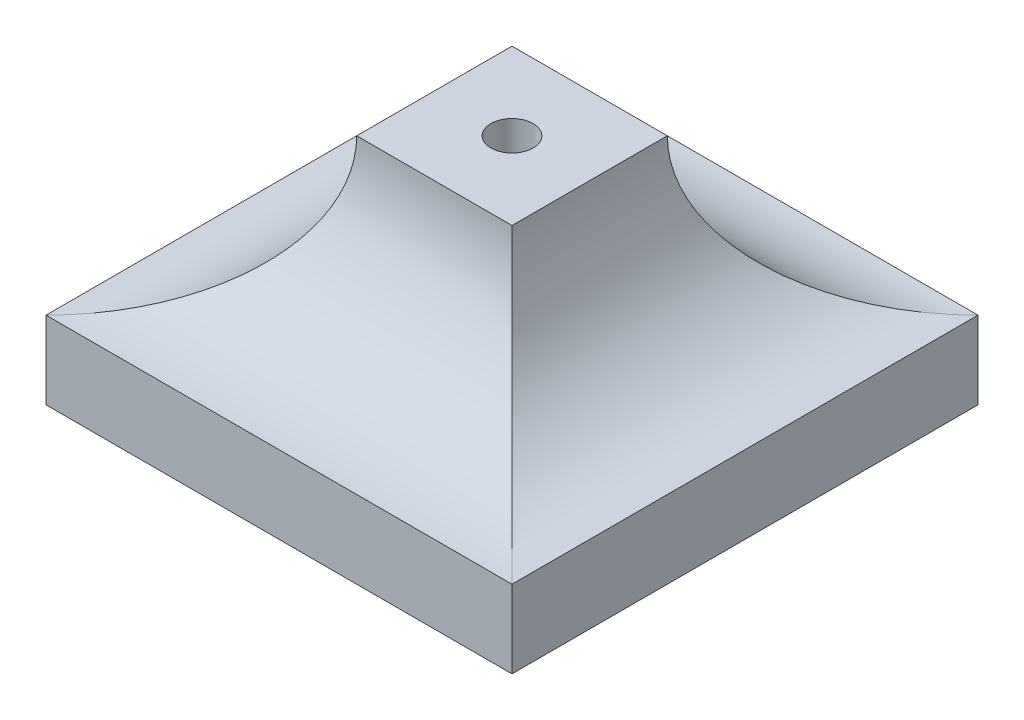
SolidWorks part; units mm, degrees
ref_plane "Front Plane" through (0, 0, 0) normal (0, 0, 1) x (1, 0, 0)
ref_plane "Top Plane" through (0, 0, 0) normal (0, 1, 0) x (1, 0, 0)
ref_plane "Right Plane" through (0, 0, 0) normal (1, 0, 0) x (0, 0, -1)
sketch "Sketch1" plane through (0, 0, 0) normal (0, 1, 0) x (1, 0, 0)
  line L1 (-19.05, 19.05) -> (19.05, 19.05)
  line L2 (-19.05, 19.05) -> (-19.05, -19.05)
  line L3 (-19.05, -19.05) -> (19.05, -19.05)
  line L4 (19.05, 19.05) -> (19.05, -19.05)
  line L5 (-19.05, 19.05) -> (19.05, -19.05) construction
  line L6 (-19.05, -19.05) -> (19.05, 19.05) construction
  point P0 (0, 0)
  dimension "D1" = 38.1
extrude "Boss-Extrude1" add sketch "Sketch1" along normal blind 6.35
sketch "Sketch2" plane through (0, 0, 19.05) normal (0, 0, 1) x (1, 0, 0)
  line L0 (-19.05, 6.35) -> (19.05, 6.35)
  line L1 (-6.35, 19.05) -> (6.35, 19.05)
  arc A0 (-19.05, 6.35) -> (-6.35, 19.05) centre (-19.05, 19.05) ccw
  arc A1 (19.05, 6.35) -> (6.35, 19.05) centre (19.05, 19.05) cw
  dimension "D1" = 12.7
extrude "Boss-Extrude2" add sketch "Sketch2" against normal up to surface (38.1 mm away) up to face at (0, 3.175, -19.05)
sketch "Sketch3" plane through (19.05, 0, 0) normal (1, 0, 0) x (0, 0, -1)
  line L0 (-19.05, 6.35) -> (-19.05, 19.05)
  line L1 (-19.05, 19.05) -> (-6.35, 19.05)
  line L2 (0, 0) -> (0, 19.05) construction
  line L3 (-19.05, 0) -> (19.05, 0) construction
  line L4 (19.05, 6.35) -> (19.05, 19.05)
  line L5 (19.05, 19.05) -> (6.35, 19.05)
  arc A0 (-19.05, 6.35) -> (-6.35, 19.05) centre (-19.05, 19.05) ccw
  arc A1 (19.05, 6.35) -> (6.35, 19.05) centre (19.05, 19.05) cw
extrude "Cut-Extrude1" cut sketch "Sketch3" against normal through all
hole_wizard "#4 Clearance Hole1" positions "Sketch4" profile "Sketch5" hole size "#4" standard "ANSI Inch" end condition through all
sketch "Sketch4" plane through (0, 19.05, 0) normal (0, 1, 0) x (1, 0, 0)
  point P0 (0, 0)
sketch "Sketch5" plane through (0, 19.05, 0) normal (1, 0, 0) x (0, 0, 1)
  line L0 (0, 0) -> (0, 19.05)
  line L1 (0, 19.05) -> (1.7272, 19.05)
  line L2 (1.7272, 19.05) -> (1.7272, 0)
  line L5 (1.7272, 0) -> (0, 0)
  line L11 (0, -6.35) -> (0, 107.95) construction
  dimension "Thru Hole Dia." = 3.4544
  dimension "Thru Hole Depth" = 19.05
sketch "Sketch6" plane through (0, 0, 0) normal (0, -1, 0) x (1, 0, 0)
  circle A0 centre (0, 0) radius 3.9688
  dimension "D1" = 7.9375
extrude "Cut-Extrude2" cut sketch "Sketch6" against normal blind 6.35
